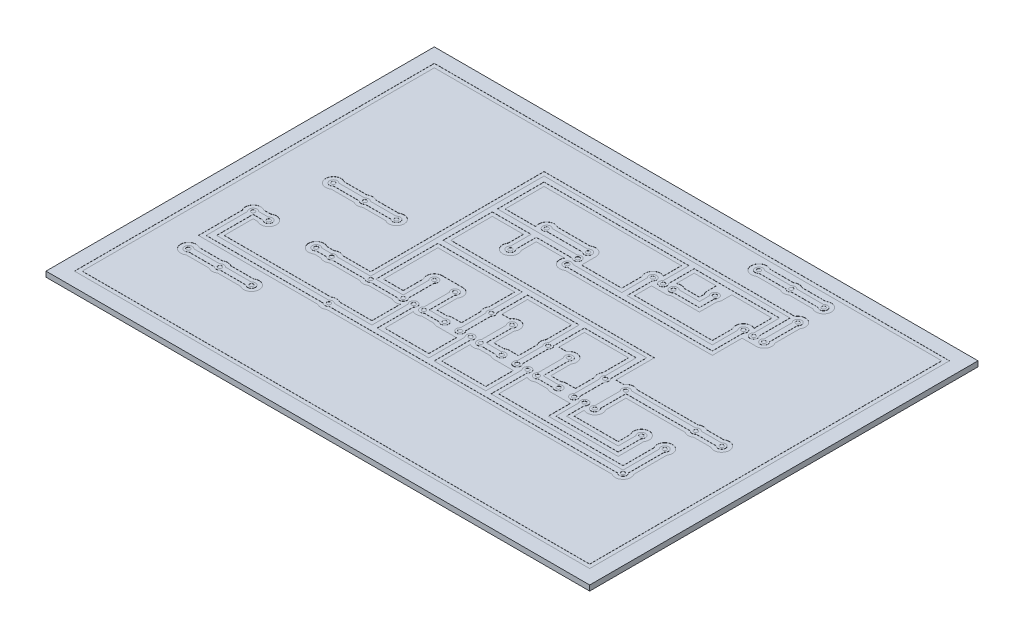
SolidWorks part; units mm, degrees
ref_plane "Front Plane" through (0, 0, 0) normal (0, 0, 1) x (1, 0, 0)
ref_plane "Top Plane" through (0, 0, 0) normal (0, 1, 0) x (1, 0, 0)
ref_plane "Right Plane" through (0, 0, 0) normal (1, 0, 0) x (0, 0, -1)
sketch "Sketch1" plane through (0, 0, 0) normal (0, 1, 0) x (1, 0, 0)
  line L0 (-86, -16.118) -> (-86, -32.118)
  line L1 (-105, 75) -> (105, 75)
  line L2 (-105, 75) -> (-105, -75)
  line L3 (-105, -75) -> (105, -75)
  line L4 (105, 75) -> (105, -75)
  line L5 (-105, 75) -> (105, -75) construction
  line L6 (-105, -75) -> (-24, -17.1429) construction
  line L7 (-86, -32.118) -> (-40.7361, -32.118)
  line L8 (75, -30) -> (75, -16.118)
  line L10 (73, -16.118) -> (73, -30)
  line L11 (72.882, -30.118) -> (22, -30.118)
  line L12 (22, -30.118) -> (22, -16.118)
  line L14 (20, -16.118) -> (20, -30.118)
  line L15 (20, -30.118) -> (0, -30.118)
  line L16 (0, -30.118) -> (0, -16.118)
  line L18 (-2, -16.118) -> (-2, -30.118)
  line L19 (-2, -30.118) -> (-22, -30.118)
  line L20 (-22, -30.118) -> (-22, -16.118)
  line L22 (-24, -16.118) -> (-24, -30.118)
  line L23 (-24, -30.118) -> (-38.5, -30.118)
  line L24 (-84, -30.118) -> (-84, -16.118)
  line L26 (-24, -17.1429) -> (-21.5529, -15.3949) construction
  line L27 (-21.5529, -15.3949) -> (105, 75) construction
  line L32 (-20, -13.882) -> (-20, -4.118)
  line L34 (-18, -4.118) -> (-18, -13.882)
  line L36 (-26, -4.118) -> (-26, -13.882)
  line L37 (-28, -13.882) -> (-28, -4.118)
  line L38 (-28.118, -16) -> (-38.5, -16)
  line L40 (-53.5, -14) -> (-40.7361, -14)
  line L42 (-38.5, -14) -> (-28.118, -14)
  line L43 (-40.7361, -16) -> (-53.5, -16)
  line L44 (4, -4.118) -> (4, -13.882)
  line L45 (2, -13.882) -> (2, -4.118)
  line L46 (-6, -13.882) -> (-6, -4.118)
  line L47 (-4, -4.118) -> (-4, -13.882)
  line L48 (24, -13.882) -> (24, -4.118)
  line L49 (16, -13.882) -> (16, -4.118)
  line L50 (26, -4.118) -> (26, -13.882)
  line L51 (18, -4.118) -> (18, -13.882)
  line L52 (48, -4.118) -> (48, -13.882)
  line L53 (38, -13.882) -> (38, -4.118)
  line L54 (46, -13.882) -> (46, -4.118)
  line L55 (40, -4.118) -> (40, -13.882)
  line L56 (44, -16.118) -> (44, -23)
  line L57 (44, -23) -> (64, -23)
  line L58 (64, -23) -> (64, -16.118)
  line L60 (66, -16.118) -> (66, -25)
  line L61 (66, -25) -> (42, -25)
  line L62 (42, -25) -> (42, -16.118)
  line L64 (40, -1.882) -> (40, 12)
  line L65 (40, 12) -> (-38.618, 12)
  line L67 (-38.618, -13.882) -> (-38.618, 10)
  line L68 (-40.618, 10) -> (-40.618, -13.882)
  line L69 (-38.618, 10) -> (-6, 10)
  line L70 (-6, 10) -> (-6, -1.882)
  line L72 (-4, -1.882) -> (-4, 10)
  line L73 (-4, 10) -> (16, 10)
  line L74 (16, 10) -> (16, -1.882)
  line L76 (18, -1.882) -> (18, 10)
  line L77 (18, 10) -> (38, 10)
  line L78 (38, 10) -> (38, -1.882)
  line L79 (48.118, -4) -> (72.882, -4)
  line L80 (-38.618, 12) -> (-38.618, 31)
  line L81 (72.882, -2) -> (48.118, -2)
  line L82 (-38.618, 31) -> (-23.618, 31)
  line L83 (-23.618, 31) -> (-23.618, 23.118)
  line L85 (-21.618, 23.118) -> (-21.618, 31)
  line L86 (-21.618, 31) -> (-7.7361, 31)
  line L88 (-7.7361, 33) -> (-38.618, 33)
  line L89 (-38.618, 33) -> (-38.618, 51)
  line L90 (-38.618, 51) -> (17.382, 51)
  line L91 (17.382, 51) -> (17.382, 41.118)
  line L93 (19.382, 41.118) -> (19.382, 51)
  line L94 (19.382, 51) -> (52.382, 51)
  line L95 (52.382, 51) -> (52.382, 41.118)
  line L97 (54.382, 41.118) -> (54.382, 53)
  line L98 (54.382, 53) -> (-40.618, 53)
  line L99 (-40.618, 53) -> (-40.618, 10)
  line L101 (-5.5, 29) -> (13.382, 29)
  line L102 (13.382, 29) -> (13.382, 38.882)
  line L104 (15.382, 38.882) -> (15.382, 29)
  line L105 (15.382, 29) -> (48.382, 29)
  line L106 (48.382, 29) -> (48.382, 38.882)
  line L108 (50.382, 38.882) -> (50.382, 27)
  line L109 (50.382, 27) -> (-5.5, 27)
  line L116 (56.2639, 62) -> (46, 62)
  line L118 (33.5, 64) -> (43.7639, 64)
  line L119 (23.5, 39) -> (31.382, 39)
  line L121 (31.382, 41) -> (23.5, 41)
  line L124 (-7.7361, 37) -> (-21.5, 37)
  line L126 (-21.5, 35) -> (-7.7361, 35)
  line L127 (58.382, 41.118) -> (58.382, 51.882)
  line L128 (56.382, 41.118) -> (56.382, 51.882)
  line L129 (-17.882, -14) -> (-12.118, -14)
  line L131 (-12.118, -16) -> (-17.882, -16)
  line L132 (4.118, -14) -> (9.882, -14)
  line L134 (9.882, -16) -> (4.118, -16)
  line L136 (26.118, -14) -> (31.882, -14)
  line L138 (31.882, -16) -> (26.118, -16)
  line L139 (-40.7361, -30.118) -> (-84, -30.118)
  line L140 (-38.5, -32.118) -> (72.882, -32.118)
  line L141 (-55.7361, -14) -> (-59.5, -14)
  line L143 (-59.5, -16) -> (-55.7361, -16)
  line L145 (-55.7361, 9) -> (-65.691, 9)
  line L147 (-77.882, 11) -> (-67.9271, 11)
  line L149 (-61.7361, -41) -> (-71.691, -41)
  line L150 (-83.882, -39) -> (-73.9271, -39)
  line L151 (-83.882, -16) -> (-80.118, -16)
  line L153 (-80.118, -14) -> (-83.882, -14)
  line L154 (-71.691, -39) -> (-61.7361, -39)
  line L155 (-73.9271, -41) -> (-83.882, -41)
  line L156 (-60.618, -40) -> (-85, -40) construction
  line L157 (-67.9271, 9) -> (-77.882, 9)
  line L158 (-65.691, 11) -> (-55.7361, 11)
  line L159 (-79, 10) -> (-54.618, 10) construction
  line L160 (75.118, -2) -> (82.882, -2)
  line L162 (82.882, -4) -> (75.118, -4)
  line L163 (46, 64) -> (56.2639, 64)
  line L164 (43.7639, 62) -> (33.5, 62)
  line L165 (57.382, 63) -> (32.382, 63) construction
  line L167 (31.382, 39) -> (33.382, 39)
  line L168 (33.382, 39) -> (33.382, 44.882)
  line L170 (31.382, 44.882) -> (31.382, 41)
  arc A1 (-84, -16.118) -> (-83.882, -16) centre (-85, -15) ccw
  circle A2 centre (-85, -15) radius 0.75
  circle A3 centre (-23, -15) radius 0.75
  arc A4 (-22, -16.118) -> (-22, -13.882) centre (-23, -15) ccw
  circle A5 centre (-1, -15) radius 0.75
  arc A6 (0, -16.118) -> (-2, -16.118) centre (-1, -15) ccw
  circle A7 centre (21, -15) radius 0.75
  arc A8 (22, -16.118) -> (20, -16.118) centre (21, -15) ccw
  circle A9 centre (74, -15) radius 0.75
  arc A10 (75, -16.118) -> (73, -16.118) centre (74, -15) ccw
  arc A11 (-24, -13.882) -> (-24, -16.118) centre (-23, -15) ccw
  circle A14 centre (-19, -15) radius 0.75
  arc A15 (-20, -13.882) -> (-17.882, -16) centre (-19, -15) ccw
  circle A16 centre (-19, -3) radius 0.75
  arc A17 (-18, -4.118) -> (-20, -4.118) centre (-19, -3) ccw
  circle A18 centre (-27, -3) radius 0.75
  circle A19 centre (-27, -15) radius 0.75
  arc A20 (-28, -13.882) -> (-28.118, -14) centre (-27, -15) ccw
  arc A21 (-26, -4.118) -> (-28, -4.118) centre (-27, -3) ccw
  circle A23 centre (-39.618, -15) radius 0.75
  arc A24 (-38.5, -14) -> (-38.618, -13.882) centre (-39.618, -15) ccw
  arc A25 (-40.7361, -16) -> (-38.5, -16) centre (-39.618, -15) ccw
  arc A26 (-28.118, -16) -> (-26, -13.882) centre (-27, -15) ccw
  circle A27 centre (3, -3) radius 0.75
  circle A28 centre (3, -15) radius 0.75
  arc A29 (2, -13.882) -> (4.118, -16) centre (3, -15) ccw
  arc A30 (4, -4.118) -> (2, -4.118) centre (3, -3) ccw
  circle A31 centre (-5, -15) radius 0.75
  arc A32 (-6, -13.882) -> (-4, -13.882) centre (-5, -15) ccw
  arc A33 (-4, -4.118) -> (-4, -1.882) centre (-5, -3) ccw
  circle A34 centre (-5, -3) radius 0.75
  arc A35 (16, -13.882) -> (18, -13.882) centre (17, -15) ccw
  circle A36 centre (17, -15) radius 0.75
  circle A37 centre (17, -3) radius 0.75
  arc A38 (24, -13.882) -> (26.118, -16) centre (25, -15) ccw
  circle A39 centre (25, -3) radius 0.75
  circle A40 centre (25, -15) radius 0.75
  arc A41 (18, -4.118) -> (18, -1.882) centre (17, -3) ccw
  arc A42 (26, -4.118) -> (24, -4.118) centre (25, -3) ccw
  circle A43 centre (39, -3) radius 0.75
  arc A44 (48, -4.118) -> (48.118, -4) centre (47, -3) ccw
  arc A45 (40, -4.118) -> (40, -1.882) centre (39, -3) ccw
  circle A46 centre (47, -3) radius 0.75
  circle A47 centre (47, -15) radius 0.75
  circle A48 centre (39, -15) radius 0.75
  arc A49 (46, -13.882) -> (48, -13.882) centre (47, -15) ccw
  arc A50 (38, -13.882) -> (40, -13.882) centre (39, -15) ccw
  circle A51 centre (43, -15) radius 0.75
  arc A52 (44, -16.118) -> (42, -16.118) centre (43, -15) ccw
  circle A53 centre (65, -15) radius 0.75
  arc A54 (66, -16.118) -> (64, -16.118) centre (65, -15) ccw
  arc A55 (-40.618, -13.882) -> (-40.7361, -14) centre (-39.618, -15) ccw
  arc A56 (38, -1.882) -> (38, -4.118) centre (39, -3) ccw
  arc A57 (16, -1.882) -> (16, -4.118) centre (17, -3) ccw
  arc A58 (-6, -1.882) -> (-6, -4.118) centre (-5, -3) ccw
  circle A59 centre (-54.618, -15) radius 0.75
  arc A60 (-53.5, -14) -> (-55.7361, -14) centre (-54.618, -15) ccw
  circle A61 centre (74, -3) radius 0.75
  arc A62 (72.882, -4) -> (75.118, -4) centre (74, -3) ccw
  arc A63 (48.118, -2) -> (46, -4.118) centre (47, -3) ccw
  circle A64 centre (-6.618, 36) radius 0.75
  arc A65 (-7.7361, 35) -> (-7.7361, 37) centre (-6.618, 36) ccw
  circle A66 centre (-22.618, 36) radius 0.75
  arc A67 (-21.5, 37) -> (-21.5, 35) centre (-22.618, 36) ccw
  circle A68 centre (-6.618, 32) radius 0.75
  arc A69 (-7.7361, 31) -> (-7.7361, 33) centre (-6.618, 32) ccw
  circle A70 centre (-22.618, 22) radius 0.75
  arc A71 (-23.618, 23.118) -> (-21.618, 23.118) centre (-22.618, 22) ccw
  circle A72 centre (-6.618, 28) radius 0.75
  arc A73 (-5.5, 29) -> (-5.5, 27) centre (-6.618, 28) ccw
  circle A74 centre (14.382, 40) radius 0.75
  arc A75 (15.382, 38.882) -> (13.382, 38.882) centre (14.382, 40) ccw
  circle A76 centre (18.382, 40) radius 0.75
  arc A77 (17.382, 41.118) -> (19.382, 41.118) centre (18.382, 40) ccw
  circle A78 centre (22.382, 40) radius 0.75
  arc A79 (23.5, 41) -> (23.5, 39) centre (22.382, 40) ccw
  circle A82 centre (49.382, 40) radius 0.75
  arc A83 (50.382, 38.882) -> (48.382, 38.882) centre (49.382, 40) ccw
  circle A84 centre (53.382, 40) radius 0.75
  arc A85 (52.382, 41.118) -> (54.382, 41.118) centre (53.382, 40) ccw
  circle A86 centre (57.382, 40) radius 0.75
  arc A87 (56.382, 41.118) -> (58.382, 41.118) centre (57.382, 40) ccw
  circle A88 centre (57.382, 53) radius 0.75
  arc A89 (58.382, 51.882) -> (56.382, 51.882) centre (57.382, 53) ccw
  circle A90 centre (57.382, 63) radius 0.75
  arc A91 (56.2639, 62) -> (56.2639, 64) centre (57.382, 63) ccw
  circle A92 centre (32.382, 63) radius 0.75
  arc A93 (33.5, 64) -> (33.5, 62) centre (32.382, 63) ccw
  arc A94 (-17.882, -14) -> (-18, -13.882) centre (-19, -15) ccw
  arc A95 (-12.118, -16) -> (-12.118, -14) centre (-11, -15) ccw
  circle A96 centre (-11, -15) radius 0.75
  circle A97 centre (11, -15) radius 0.75
  arc A98 (9.882, -16) -> (9.882, -14) centre (11, -15) ccw
  arc A99 (4.118, -14) -> (4, -13.882) centre (3, -15) ccw
  circle A100 centre (33, -15) radius 0.75
  arc A101 (31.882, -16) -> (31.882, -14) centre (33, -15) ccw
  arc A102 (26.118, -14) -> (26, -13.882) centre (25, -15) ccw
  circle A103 centre (-39.618, -31.118) radius 0.75
  arc A104 (-38.5, -30.118) -> (-40.7361, -30.118) centre (-39.618, -31.118) ccw
  circle A105 centre (74, -31.118) radius 0.75
  arc A106 (73, -30) -> (72.882, -30.118) centre (74, -31.118) ccw
  circle A109 centre (-54.618, 10) radius 0.75
  arc A110 (-55.7361, 9) -> (-55.7361, 11) centre (-54.618, 10) ccw
  arc A111 (-40.7361, -32.118) -> (-38.5, -32.118) centre (-39.618, -31.118) ccw
  arc A112 (72.882, -32.118) -> (75, -30) centre (74, -31.118) ccw
  circle A113 centre (-60.618, -15) radius 0.75
  arc A114 (-59.5, -14) -> (-59.5, -16) centre (-60.618, -15) ccw
  arc A115 (-55.7361, -16) -> (-53.5, -16) centre (-54.618, -15) ccw
  circle A116 centre (-79, 10) radius 0.75
  arc A117 (-77.882, 11) -> (-77.882, 9) centre (-79, 10) ccw
  circle A118 centre (-60.618, -40) radius 0.75
  arc A119 (-61.7361, -41) -> (-61.7361, -39) centre (-60.618, -40) ccw
  circle A120 centre (-85, -40) radius 0.75
  arc A121 (-83.882, -39) -> (-83.882, -41) centre (-85, -40) ccw
  circle A122 centre (-79, -15) radius 0.75
  arc A123 (-80.118, -16) -> (-80.118, -14) centre (-79, -15) ccw
  arc A124 (-83.882, -14) -> (-86, -16.118) centre (-85, -15) ccw
  circle A125 centre (-66.809, 10) radius 0.75
  arc A126 (-65.691, 11) -> (-67.9271, 11) centre (-66.809, 10) ccw
  arc A127 (-71.691, -39) -> (-73.9271, -39) centre (-72.809, -40) ccw
  circle A128 centre (-72.809, -40) radius 0.75
  arc A129 (-73.9271, -41) -> (-71.691, -41) centre (-72.809, -40) ccw
  arc A130 (-67.9271, 9) -> (-65.691, 9) centre (-66.809, 10) ccw
  arc A131 (-22, -13.882) -> (-24, -13.882) centre (-23, -15) ccw
  circle A132 centre (84, -3) radius 0.75
  arc A133 (82.882, -4) -> (82.882, -2) centre (84, -3) ccw
  arc A134 (75.118, -2) -> (72.882, -2) centre (74, -3) ccw
  arc A135 (46, 64) -> (43.7639, 64) centre (44.882, 63) ccw
  circle A136 centre (44.882, 63) radius 0.75
  arc A137 (43.7639, 62) -> (46, 62) centre (44.882, 63) ccw
  circle A138 centre (32.382, 46) radius 0.75
  arc A139 (33.382, 44.882) -> (31.382, 44.882) centre (32.382, 46) ccw
  point P0 (0, 0)
  point P289 (-66.809, 10)
  point P290 (-72.809, -40)
  point P291 (44.882, 63)
  dimension "D1" = 150
  dimension "D3" = 3
  dimension "D6" = 1.5
  dimension "D15" = 3
  dimension "D16" = 1.5
  dimension "D17" = 3
  dimension "D18" = 1.5
  dimension "D19" = 3
  dimension "D20" = 1.5
  dimension "D21" = 1.5
  dimension "D22" = 3
  dimension "D26" = 15
  dimension "D27" = 10
  dimension "D29" = 1.5
  dimension "D30" = 3
  dimension "D33" = 3
  dimension "D34" = 1.5
  dimension "D35" = 1.5
  dimension "D36" = 1.5
  dimension "D43" = 1.5
  dimension "D44" = 3
  dimension "D52" = 4
  dimension "D59" = 3
  dimension "D60" = 1.5
  dimension "D61" = 3
  dimension "D62" = 1.5
  dimension "D71" = 15
  dimension "D89" = 4
  dimension "D90" = 3
  dimension "D84" = 4
  dimension "D116" = 3
  dimension "D117" = 1.5
  dimension "D100" = 1.5
  dimension "D2" = 210
  dimension "D4" = 15
  dimension "D5" = 20
  dimension "D7" = 2
  dimension "D8" = 2
  dimension "D9" = 2
  dimension "D10" = 60
  dimension "D11" = 20
  dimension "D12" = 20
  dimension "D13" = 8
  dimension "D14" = 14
  dimension "D23" = 2
  dimension "D24" = 2
  dimension "D25" = 25
  dimension "D28" = 4
  dimension "D31" = 2
  dimension "D32" = 12
  dimension "D37" = 26
  dimension "D38" = 27
  dimension "D39" = 3
  dimension "D40" = 13.882
  dimension "D41" = 2
  dimension "D42" = 2
  dimension "D45" = 38.5
  dimension "D46" = 2
  dimension "D47" = 2
  dimension "D48" = 2
  dimension "D49" = 4
  dimension "D50" = 4
  dimension "D51" = 4
  dimension "D53" = 2
  dimension "D54" = 2
  dimension "D55" = 2
  dimension "D56" = 2
  dimension "D57" = 2
  dimension "D58" = 2
  dimension "D63" = 20
  dimension "D64" = 4
  dimension "D65" = 4
  dimension "D66" = 20
  dimension "D67" = 8
  dimension "D68" = 10
  dimension "D69" = 2
  dimension "D70" = 2
  dimension "D72" = 2
  dimension "D73" = 2
  dimension "D74" = 2
  dimension "D75" = 2
  dimension "D76" = 2
  dimension "D77" = 2
  dimension "D78" = 2
  dimension "D79" = 2
  dimension "D80" = 2
  dimension "D81" = 2
  dimension "D82" = 2
  dimension "D83" = 2
  dimension "D85" = 2
  dimension "D86" = 4
  dimension "D87" = 2
  dimension "D88" = 4
  dimension "D91" = 2
  dimension "D92" = 10
  dimension "D93" = 4
  dimension "D94" = 4
  dimension "D95" = 10
  dimension "D96" = 15
  dimension "D97" = 20
  dimension "D98" = 10
  dimension "D99" = 15
  dimension "D101" = 10
  dimension "D102" = 8
  dimension "D103" = 8
  dimension "D104" = 8
  dimension "D105" = 1
  dimension "D106" = 25
  dimension "D107" = 2
  dimension "D108" = 2
  dimension "D109" = 25
  dimension "D110" = 6
  dimension "D111" = 5
  dimension "D112" = 15
  dimension "D114" = 2
  dimension "D115" = 6
extrude "Boss-Extrude3" add sketch "Sketch1" along normal blind 2 contours L1 L4 L3 L2
extrude "Boss-Extrude4" add sketch "Sketch1<5>" along normal blind 2.05 contours A11 L22 L23 L24 A1 L0 L7 L8 A10 L10 L11 L12 A8 L14 L15 L16 A6 L18 L19 L20 A4 A2 A3 A5 A7 A9 | L60 A54 L58 L57 L56 A52 L62 L61 A51 A53 | L54 A49 L52 A44 A46 A47 | L53 A50 L55 A45 A43 A48 | L50 A42 L48 A38 A39 A40 | L51 A41 L49 A35 A36 A37 | L44 A30 L45 A29 A27 A28 | L47 A33 L46 A32 A34 A31 | L34 A17 L32 A15 A14 A16 | L38 A26 L36 A21 L37 A20 L42 A24 L40 L43 A25 A18 A19 A23 | L118 A93 L116 A91 A90 A92 | L124 A67 L126 A65 A64 A66 | L108 A83 L106 L105 L104 A75 L102 L101 A73 L109 A72 A74 A82 | L119 L121 A79 A78 A138 | L127 A89 L128 A87 A86 A88 | L157 A130 L145 A110 L158 A126 L147 A117 A109 A116 A125 | L155 A129 L149 A119 L154 A127 L150 A121 A118 A120 A128 region at (-85.9453, 0, 14.0547) region at (-19.814, 0, 9) region at (-27.3609, 0, 9) region at (3.814, 0, 9) region at (24.186, 0, 9) region at (47.5728, 0, 9) region at (43.7248, 0, 19.559) region at (3.941, 0, -28.3912) region at (51.132, 0, -62.2816) region at (21.0401, 0, -40) region at (-14.618, 0, -36) region at (57.382, 0, -46.5) region at (-60.7135, 0, -9.2755) region at (-66.7135, 0, 40.7245)
sketch "Sketch1<5>" plane through (0, 0, 0) normal (0, 1, 0) x (1, 0, 0) same geometry as "Sketch1"
sketch "Sketch2" plane through (0, 2, 0) normal (0, 1, 0) x (1, 0, 0)
  line L0 (41.5, -1.3417) -> (44.5, -1.3417)
  line L1 (-105, 75) -> (105, 75)
  line L2 (-105, 75) -> (-105, -75)
  line L3 (-105, -75) -> (105, -75)
  line L4 (59.882, 41.6583) -> (59.882, 51.3417)
  line L5 (54.882, 51.3417) -> (54.882, 41.6583)
  line L6 (59.882, 41.6583) -> (59.882, 51.3417)
  line L8 (105, 75) -> (105, -75)
  line L9 (19.5, -1.3417) -> (22.5, -1.3417)
  line L10 (-2.5, -1.3417) -> (0.5, -1.3417)
  line L11 (-27, 0) -> (-19, 0)
  line L12 (57.382, 37) -> (51.882, 37)
  line L13 (22.382, 37) -> (16.882, 37)
  line L14 (34.0403, 60.5) -> (43.2237, 60.5)
  line L15 (46.5403, 60.5) -> (55.7237, 60.5)
  line L16 (55.7237, 65.5) -> (46.5403, 65.5)
  line L17 (43.2237, 65.5) -> (34.0403, 65.5)
  line L18 (34.0403, 60.5) -> (43.2237, 60.5)
  line L19 (46.5403, 60.5) -> (55.7237, 60.5)
  line L20 (55.7237, 65.5) -> (46.5403, 65.5)
  line L21 (43.2237, 65.5) -> (34.0403, 65.5)
  line L22 (-3.618, 36) -> (-3.618, 30.5)
  line L23 (29.382, 46) -> (29.382, 49.5)
  line L24 (35.382, 46) -> (35.382, 49.5)
  line L25 (-11, -18) -> (-5, -18)
  line L26 (-11, -12) -> (-7.5, -12)
  line L27 (11, -12) -> (14.5, -12)
  line L28 (33, -12) -> (36.5, -12)
  line L29 (33, -18) -> (40.5, -18)
  line L30 (11, -18) -> (18.5, -18)
  line L31 (-5, -18) -> (-3.5, -18)
  line L74 (-17.3417, -17.5) -> (-12.6583, -17.5)
  line L75 (-12.6583, -12.5) -> (-16.5, -12.5)
  line L76 (-16.5, -12.5) -> (-16.5, -4.6583)
  line L77 (-21.5, -4.6583) -> (-21.5, -13.3417)
  line L78 (-17.3417, -17.5) -> (-12.6583, -17.5)
  line L79 (-12.6583, -12.5) -> (-16.5, -12.5)
  line L80 (-16.5, -12.5) -> (-16.5, -4.6583)
  line L85 (-25.5, -16.6583) -> (-25.5, -28.618)
  line L86 (-25.5, -28.618) -> (-37.9597, -28.618)
  line L87 (-58.9597, -17.5) -> (-56.2763, -17.5)
  line L88 (-52.9597, -17.5) -> (-41.2763, -17.5)
  line L89 (-37.9597, -17.5) -> (-28.6583, -17.5)
  line L90 (-24.5, -13.3417) -> (-24.5, -4.6583)
  line L91 (-29.5, -4.6583) -> (-29.5, -12.5)
  line L92 (-29.5, -12.5) -> (-37.118, -12.5)
  line L93 (-37.118, -12.5) -> (-37.118, 8.5)
  line L94 (-37.118, 8.5) -> (-7.5, 8.5)
  line L95 (-7.5, 8.5) -> (-7.5, -1.3417)
  line L96 (-7.5, -4.6583) -> (-7.5, -13.3417)
  line L97 (-2.5, -13.3417) -> (-2.5, -4.6583)
  line L98 (-2.5, -1.3417) -> (-2.5, 8.5)
  line L99 (-2.5, 8.5) -> (14.5, 8.5)
  line L100 (14.5, 8.5) -> (14.5, -1.3417)
  line L101 (14.5, -4.6583) -> (14.5, -13.3417)
  line L102 (19.5, -13.3417) -> (19.5, -4.6583)
  line L103 (19.5, -1.3417) -> (19.5, 8.5)
  line L104 (19.5, 8.5) -> (36.5, 8.5)
  line L105 (36.5, 8.5) -> (36.5, -1.3417)
  line L106 (36.5, -4.6583) -> (36.5, -13.3417)
  line L107 (41.5, -13.3417) -> (41.5, -4.6583)
  line L108 (41.5, -1.3417) -> (41.5, 13.5)
  line L109 (41.5, 13.5) -> (-37.118, 13.5)
  line L110 (-37.118, 13.5) -> (-37.118, 29.5)
  line L111 (-37.118, 29.5) -> (-25.118, 29.5)
  line L112 (-25.118, 29.5) -> (-25.118, 23.6583)
  line L113 (-20.118, 23.6583) -> (-20.118, 29.5)
  line L114 (-20.118, 29.5) -> (-8.2763, 29.5)
  line L115 (-8.2763, 34.5) -> (-37.118, 34.5)
  line L116 (-37.118, 34.5) -> (-37.118, 49.5)
  line L117 (-37.118, 49.5) -> (15.882, 49.5)
  line L118 (15.882, 49.5) -> (15.882, 41.6583)
  line L119 (20.882, 41.6583) -> (20.882, 49.5)
  line L120 (20.882, 49.5) -> (50.882, 49.5)
  line L121 (50.882, 49.5) -> (50.882, 41.6583)
  line L122 (55.882, 41.6583) -> (55.882, 54.5)
  line L123 (55.882, 54.5) -> (-42.118, 54.5)
  line L124 (-42.118, 54.5) -> (-42.118, -12.5)
  line L125 (-42.118, -12.5) -> (-52.9597, -12.5)
  line L126 (-56.2763, -12.5) -> (-58.9597, -12.5)
  line L127 (-58.9597, -17.5) -> (-56.2763, -17.5)
  line L128 (-52.9597, -17.5) -> (-41.2763, -17.5)
  line L129 (-37.9597, -17.5) -> (-28.6583, -17.5)
  line L131 (-29.5, -4.6583) -> (-29.5, -12.5)
  line L132 (-29.5, -12.5) -> (-37.118, -12.5)
  line L133 (-37.118, -12.5) -> (-37.118, 8.5)
  line L134 (-37.118, 8.5) -> (-7.5, 8.5)
  line L135 (-7.5, 8.5) -> (-7.5, -1.3417)
  line L136 (-7.5, -4.6583) -> (-7.5, -12)
  line L138 (-2.5, -1.3417) -> (-2.5, 8.5)
  line L139 (-2.5, 8.5) -> (14.5, 8.5)
  line L140 (14.5, 8.5) -> (14.5, -1.3417)
  line L141 (14.5, -4.6583) -> (14.5, -12)
  line L143 (19.5, -1.3417) -> (19.5, 8.5)
  line L144 (19.5, 8.5) -> (36.5, 8.5)
  line L145 (36.5, 8.5) -> (36.5, -1.3417)
  line L146 (36.5, -4.6583) -> (36.5, -12)
  line L148 (41.5, -1.3417) -> (41.5, 13.5)
  line L149 (41.5, 13.5) -> (-37.118, 13.5)
  line L150 (-37.118, 13.5) -> (-37.118, 29.5)
  line L151 (-37.118, 29.5) -> (-25.118, 29.5)
  line L152 (-25.118, 29.5) -> (-25.118, 23.6583)
  line L153 (-20.118, 23.6583) -> (-20.118, 29.5)
  line L154 (-20.118, 29.5) -> (-9.2161, 29.5)
  line L155 (-25.2161, 34.5) -> (-37.118, 34.5)
  line L156 (-37.118, 34.5) -> (-37.118, 49.5)
  line L157 (-37.118, 49.5) -> (15.882, 49.5)
  line L158 (15.882, 49.5) -> (15.882, 42.5981)
  line L159 (20.882, 42.5981) -> (20.882, 49.5)
  line L160 (20.882, 49.5) -> (50.882, 49.5)
  line L161 (50.882, 49.5) -> (50.882, 42.5981)
  line L163 (54.7839, 54.5) -> (-42.118, 54.5)
  line L164 (-42.118, 54.5) -> (-42.118, -12.5)
  line L165 (-42.118, -12.5) -> (-52.9597, -12.5)
  line L166 (-56.2763, -12.5) -> (-58.9597, -12.5)
  line L167 (-41.2763, -28.618) -> (-82.5, -28.618)
  line L168 (-82.5, -28.618) -> (-82.5, -17.5)
  line L169 (-82.5, -17.5) -> (-80.6583, -17.5)
  line L170 (-80.6583, -12.5) -> (-83.3417, -12.5)
  line L171 (-87.5, -16.6583) -> (-87.5, -33.618)
  line L172 (-87.5, -33.618) -> (-41.2763, -33.618)
  line L173 (-37.9597, -33.618) -> (72.3417, -33.618)
  line L174 (76.5, -29.4597) -> (76.5, -16.6583)
  line L175 (71.5, -16.6583) -> (71.5, -28.618)
  line L176 (71.5, -28.618) -> (23.5, -28.618)
  line L177 (23.5, -28.618) -> (23.5, -16.6583)
  line L178 (18.5, -16.6583) -> (18.5, -28.618)
  line L179 (18.5, -28.618) -> (1.5, -28.618)
  line L180 (1.5, -28.618) -> (1.5, -16.6583)
  line L181 (-3.5, -16.6583) -> (-3.5, -28.618)
  line L182 (-3.5, -28.618) -> (-20.5, -28.618)
  line L183 (-20.5, -28.618) -> (-20.5, -16.6583)
  line L184 (-25.5, -17.5981) -> (-25.5, -28.618)
  line L185 (-25.5, -28.618) -> (-37.9597, -28.618)
  line L186 (-41.2763, -28.618) -> (-82.5, -28.618)
  line L187 (-82.5, -28.618) -> (-82.5, -17.5)
  line L188 (-82.5, -17.5) -> (-80.6583, -17.5)
  line L189 (-80.6583, -12.5) -> (-83.3417, -12.5)
  line L190 (-87.5, -16.6583) -> (-87.5, -33.618)
  line L191 (-87.5, -33.618) -> (-41.2763, -33.618)
  line L192 (-37.9597, -33.618) -> (72.3417, -33.618)
  line L193 (76.5, -29.4597) -> (76.5, -16.6583)
  line L194 (71.5, -16.6583) -> (71.5, -28.618)
  line L195 (71.5, -28.618) -> (23.5, -28.618)
  line L196 (23.5, -28.618) -> (23.5, -16.6583)
  line L197 (18.5, -18) -> (18.5, -28.618)
  line L198 (18.5, -28.618) -> (1.5, -28.618)
  line L199 (1.5, -28.618) -> (1.5, -17.5981)
  line L200 (-3.5, -18) -> (-3.5, -28.618)
  line L201 (-3.5, -28.618) -> (-20.5, -28.618)
  line L202 (-20.5, -28.618) -> (-20.5, -17.5981)
  line L204 (9.3417, -12.5) -> (5.5, -12.5)
  line L205 (5.5, -12.5) -> (5.5, -4.6583)
  line L206 (0.5, -4.6583) -> (0.5, -13.3417)
  line L207 (4.6583, -17.5) -> (9.3417, -17.5)
  line L208 (9.3417, -12.5) -> (5.5, -12.5)
  line L209 (5.5, -12.5) -> (5.5, -4.6583)
  line L211 (4.6583, -17.5) -> (9.3417, -17.5)
  line L216 (31.3417, -12.5) -> (27.5, -12.5)
  line L217 (27.5, -12.5) -> (27.5, -4.6583)
  line L218 (22.5, -4.6583) -> (22.5, -13.3417)
  line L219 (26.6583, -17.5) -> (31.3417, -17.5)
  line L220 (31.3417, -12.5) -> (27.5, -12.5)
  line L221 (27.5, -12.5) -> (27.5, -4.6583)
  line L223 (26.6583, -17.5) -> (31.3417, -17.5)
  line L232 (67.5, -26.5) -> (67.5, -16.6583)
  line L233 (62.5, -16.6583) -> (62.5, -21.5)
  line L234 (62.5, -21.5) -> (45.5, -21.5)
  line L235 (45.5, -21.5) -> (45.5, -16.6583)
  line L236 (40.5, -16.6583) -> (40.5, -26.5)
  line L237 (40.5, -26.5) -> (67.5, -26.5)
  line L238 (67.5, -26.5) -> (67.5, -16.6583)
  line L239 (62.5, -16.6583) -> (62.5, -21.5)
  line L240 (62.5, -21.5) -> (45.5, -21.5)
  line L241 (45.5, -21.5) -> (45.5, -17.5981)
  line L242 (40.5, -18) -> (40.5, -26.5)
  line L243 (40.5, -26.5) -> (67.5, -26.5)
  line L250 (82.3417, -0.5) -> (75.6583, -0.5)
  line L251 (72.3417, -0.5) -> (48.6583, -0.5)
  line L252 (44.5, -4.6583) -> (44.5, -13.3417)
  line L253 (49.5, -13.3417) -> (49.5, -5.5)
  line L254 (49.5, -5.5) -> (72.3417, -5.5)
  line L255 (75.6583, -5.5) -> (82.3417, -5.5)
  line L256 (82.3417, -0.5) -> (75.6583, -0.5)
  line L257 (72.3417, -0.5) -> (48.6583, -0.5)
  line L259 (49.5, -13.3417) -> (49.5, -5.5)
  line L260 (49.5, -5.5) -> (72.3417, -5.5)
  line L261 (75.6583, -5.5) -> (82.3417, -5.5)
  line L270 (51.882, 25.5) -> (51.882, 38.3417)
  line L271 (46.882, 38.3417) -> (46.882, 30.5)
  line L272 (46.882, 30.5) -> (16.882, 30.5)
  line L273 (16.882, 30.5) -> (16.882, 38.3417)
  line L274 (11.882, 38.3417) -> (11.882, 30.5)
  line L275 (11.882, 30.5) -> (-4.9597, 30.5)
  line L276 (-4.9597, 25.5) -> (51.882, 25.5)
  line L277 (51.882, 25.5) -> (51.882, 37)
  line L278 (46.882, 38.3417) -> (46.882, 30.5)
  line L279 (46.882, 30.5) -> (16.882, 30.5)
  line L280 (16.882, 30.5) -> (16.882, 37)
  line L281 (11.882, 38.3417) -> (11.882, 30.5)
  line L282 (11.882, 30.5) -> (-3.618, 30.5)
  line L283 (-4.9597, 25.5) -> (51.882, 25.5)
  line L285 (34.882, 37.5) -> (34.882, 44.3417)
  line L286 (29.882, 44.3417) -> (29.882, 42.5)
  line L287 (29.882, 42.5) -> (24.0403, 42.5)
  line L288 (24.0403, 37.5) -> (34.882, 37.5)
  line L289 (34.882, 37.5) -> (34.882, 44.3417)
  line L290 (29.882, 44.3417) -> (29.882, 42.5)
  line L291 (29.882, 42.5) -> (24.0403, 42.5)
  line L292 (24.0403, 37.5) -> (34.882, 37.5)
  line L293 (-8.2763, 38.5) -> (-20.9597, 38.5)
  line L294 (-20.9597, 33.5) -> (-8.2763, 33.5)
  line L295 (-8.2763, 38.5) -> (-20.9597, 38.5)
  line L303 (-77.3417, 7.5) -> (-68.4673, 7.5)
  line L304 (-65.1507, 7.5) -> (-56.2763, 7.5)
  line L305 (-56.2763, 12.5) -> (-65.1507, 12.5)
  line L306 (-68.4673, 12.5) -> (-77.3417, 12.5)
  line L307 (-77.3417, 7.5) -> (-68.4673, 7.5)
  line L308 (-65.1507, 7.5) -> (-56.2763, 7.5)
  line L309 (-56.2763, 12.5) -> (-65.1507, 12.5)
  line L310 (-68.4673, 12.5) -> (-77.3417, 12.5)
  line L315 (-83.3417, -42.5) -> (-74.4673, -42.5)
  line L316 (-71.1507, -42.5) -> (-62.2763, -42.5)
  line L317 (-62.2763, -37.5) -> (-71.1507, -37.5)
  line L318 (-74.4673, -37.5) -> (-83.3417, -37.5)
  line L319 (-83.3417, -42.5) -> (-74.4673, -42.5)
  line L320 (-71.1507, -42.5) -> (-62.2763, -42.5)
  line L321 (-62.2763, -37.5) -> (-71.1507, -37.5)
  line L322 (-74.4673, -37.5) -> (-83.3417, -37.5)
  arc A0 (22.382, 37) -> (24.0403, 37.5) centre (22.382, 40) ccw
  arc A1 (29.382, 46) -> (29.882, 44.3417) centre (32.382, 46) ccw
  arc A2 (-11, -12) -> (-12.6583, -12.5) centre (-11, -15) ccw
  arc A3 (11, -12) -> (9.3417, -12.5) centre (11, -15) ccw
  arc A4 (33, -12) -> (31.3417, -12.5) centre (33, -15) ccw
  arc A5 (59.882, 51.3417) -> (54.882, 51.3417) centre (57.382, 53) ccw
  arc A6 (54.882, 41.6583) -> (59.882, 41.6583) centre (57.382, 40) ccw
  arc A7 (59.882, 51.3417) -> (54.7839, 54.5) centre (57.382, 53) ccw
  arc A8 (57.382, 37) -> (59.882, 41.6583) centre (57.382, 40) ccw
  arc A15 (43.2237, 60.5) -> (46.5403, 60.5) centre (44.882, 63) ccw
  arc A16 (55.7237, 60.5) -> (55.7237, 65.5) centre (57.382, 63) ccw
  arc A17 (46.5403, 65.5) -> (43.2237, 65.5) centre (44.882, 63) ccw
  arc A18 (34.0403, 65.5) -> (34.0403, 60.5) centre (32.382, 63) ccw
  arc A19 (43.2237, 60.5) -> (46.5403, 60.5) centre (44.882, 63) ccw
  arc A20 (55.7237, 60.5) -> (55.7237, 65.5) centre (57.382, 63) ccw
  arc A21 (46.5403, 65.5) -> (43.2237, 65.5) centre (44.882, 63) ccw
  arc A22 (34.0403, 65.5) -> (34.0403, 60.5) centre (32.382, 63) ccw
  arc A44 (-12.6583, -17.5) -> (-12.6583, -12.5) centre (-11, -15) ccw
  arc A45 (-16.5, -4.6583) -> (-21.5, -4.6583) centre (-19, -3) ccw
  arc A46 (-21.5, -13.3417) -> (-17.3417, -17.5) centre (-19, -15) ccw
  arc A47 (-56.2763, -17.5) -> (-52.9597, -17.5) centre (-54.618, -15) ccw
  arc A48 (-41.2763, -17.5) -> (-37.9597, -17.5) centre (-39.618, -15) ccw
  arc A49 (-28.6583, -17.5) -> (-24.5, -13.3417) centre (-27, -15) ccw
  arc A50 (-24.5, -4.6583) -> (-29.5, -4.6583) centre (-27, -3) ccw
  arc A51 (-7.5, -1.3417) -> (-7.5, -4.6583) centre (-5, -3) ccw
  arc A52 (-7.5, -13.3417) -> (-2.5, -13.3417) centre (-5, -15) ccw
  arc A53 (-2.5, -4.6583) -> (-2.5, -1.3417) centre (-5, -3) ccw
  arc A54 (14.5, -1.3417) -> (14.5, -4.6583) centre (17, -3) ccw
  arc A55 (14.5, -13.3417) -> (19.5, -13.3417) centre (17, -15) ccw
  arc A56 (19.5, -4.6583) -> (19.5, -1.3417) centre (17, -3) ccw
  arc A57 (36.5, -1.3417) -> (36.5, -4.6583) centre (39, -3) ccw
  arc A58 (36.5, -13.3417) -> (41.5, -13.3417) centre (39, -15) ccw
  arc A59 (41.5, -4.6583) -> (41.5, -1.3417) centre (39, -3) ccw
  arc A60 (-25.118, 23.6583) -> (-20.118, 23.6583) centre (-22.618, 22) ccw
  arc A61 (-8.2763, 29.5) -> (-8.2763, 34.5) centre (-6.618, 32) ccw
  arc A62 (15.882, 41.6583) -> (20.882, 41.6583) centre (18.382, 40) ccw
  arc A63 (50.882, 41.6583) -> (55.882, 41.6583) centre (53.382, 40) ccw
  arc A64 (-52.9597, -12.5) -> (-56.2763, -12.5) centre (-54.618, -15) ccw
  arc A65 (-58.9597, -12.5) -> (-58.9597, -17.5) centre (-60.618, -15) ccw
  arc A66 (-56.2763, -17.5) -> (-52.9597, -17.5) centre (-54.618, -15) ccw
  arc A67 (-41.2763, -17.5) -> (-37.9597, -17.5) centre (-39.618, -15) ccw
  arc A68 (-28.6583, -17.5) -> (-25.5, -17.5981) centre (-27, -15) ccw
  arc A69 (-27, 0) -> (-29.5, -4.6583) centre (-27, -3) ccw
  arc A70 (-7.5, -1.3417) -> (-7.5, -4.6583) centre (-5, -3) ccw
  arc A73 (14.5, -1.3417) -> (14.5, -4.6583) centre (17, -3) ccw
  arc A76 (36.5, -1.3417) -> (36.5, -4.6583) centre (39, -3) ccw
  arc A79 (-25.118, 23.6583) -> (-20.118, 23.6583) centre (-22.618, 22) ccw
  arc A83 (-52.9597, -12.5) -> (-56.2763, -12.5) centre (-54.618, -15) ccw
  arc A84 (-58.9597, -12.5) -> (-58.9597, -17.5) centre (-60.618, -15) ccw
  arc A85 (-20.5, -16.6583) -> (-25.5, -16.6583) centre (-23, -15) ccw
  arc A86 (-37.9597, -28.618) -> (-41.2763, -28.618) centre (-39.618, -31.118) ccw
  arc A87 (-80.6583, -17.5) -> (-80.6583, -12.5) centre (-79, -15) ccw
  arc A88 (-83.3417, -12.5) -> (-87.5, -16.6583) centre (-85, -15) ccw
  arc A89 (-41.2763, -33.618) -> (-37.9597, -33.618) centre (-39.618, -31.118) ccw
  arc A90 (72.3417, -33.618) -> (76.5, -29.4597) centre (74, -31.118) ccw
  arc A91 (76.5, -16.6583) -> (71.5, -16.6583) centre (74, -15) ccw
  arc A92 (23.5, -16.6583) -> (18.5, -16.6583) centre (21, -15) ccw
  arc A93 (1.5, -16.6583) -> (-3.5, -16.6583) centre (-1, -15) ccw
  arc A95 (-37.9597, -28.618) -> (-41.2763, -28.618) centre (-39.618, -31.118) ccw
  arc A96 (-80.6583, -17.5) -> (-80.6583, -12.5) centre (-79, -15) ccw
  arc A97 (-83.3417, -12.5) -> (-87.5, -16.6583) centre (-85, -15) ccw
  arc A98 (-41.2763, -33.618) -> (-37.9597, -33.618) centre (-39.618, -31.118) ccw
  arc A99 (72.3417, -33.618) -> (76.5, -29.4597) centre (74, -31.118) ccw
  arc A100 (76.5, -16.6583) -> (71.5, -16.6583) centre (74, -15) ccw
  arc A103 (-12.6583, -17.5) -> (-11, -18) centre (-11, -15) ccw
  arc A104 (-16.5, -4.6583) -> (-19, 0) centre (-19, -3) ccw
  arc A105 (-20.5, -17.5981) -> (-17.3417, -17.5) centre (-19, -15) ccw
  arc A110 (5.5, -4.6583) -> (0.5, -4.6583) centre (3, -3) ccw
  arc A111 (0.5, -13.3417) -> (4.6583, -17.5) centre (3, -15) ccw
  arc A112 (9.3417, -17.5) -> (9.3417, -12.5) centre (11, -15) ccw
  arc A113 (5.5, -4.6583) -> (0.5, -1.3417) centre (3, -3) ccw
  arc A114 (1.5, -17.5981) -> (4.6583, -17.5) centre (3, -15) ccw
  arc A115 (9.3417, -17.5) -> (11, -18) centre (11, -15) ccw
  arc A120 (27.5, -4.6583) -> (22.5, -4.6583) centre (25, -3) ccw
  arc A121 (22.5, -13.3417) -> (26.6583, -17.5) centre (25, -15) ccw
  arc A122 (31.3417, -17.5) -> (31.3417, -12.5) centre (33, -15) ccw
  arc A123 (27.5, -4.6583) -> (22.5, -1.3417) centre (25, -3) ccw
  arc A124 (23.5, -17.5981) -> (26.6583, -17.5) centre (25, -15) ccw
  arc A125 (31.3417, -17.5) -> (33, -18) centre (33, -15) ccw
  arc A126 (67.5, -16.6583) -> (62.5, -16.6583) centre (65, -15) ccw
  arc A127 (45.5, -16.6583) -> (40.5, -16.6583) centre (43, -15) ccw
  arc A128 (67.5, -16.6583) -> (62.5, -16.6583) centre (65, -15) ccw
  arc A140 (75.6583, -0.5) -> (72.3417, -0.5) centre (74, -3) ccw
  arc A141 (48.6583, -0.5) -> (44.5, -4.6583) centre (47, -3) ccw
  arc A142 (44.5, -13.3417) -> (49.5, -13.3417) centre (47, -15) ccw
  arc A143 (72.3417, -5.5) -> (75.6583, -5.5) centre (74, -3) ccw
  arc A144 (82.3417, -5.5) -> (82.3417, -0.5) centre (84, -3) ccw
  arc A145 (75.6583, -0.5) -> (72.3417, -0.5) centre (74, -3) ccw
  arc A146 (48.6583, -0.5) -> (44.5, -1.3417) centre (47, -3) ccw
  arc A147 (45.5, -17.5981) -> (49.5, -13.3417) centre (47, -15) ccw
  arc A148 (72.3417, -5.5) -> (75.6583, -5.5) centre (74, -3) ccw
  arc A149 (82.3417, -5.5) -> (82.3417, -0.5) centre (84, -3) ccw
  arc A150 (51.882, 38.3417) -> (46.882, 38.3417) centre (49.382, 40) ccw
  arc A151 (16.882, 38.3417) -> (11.882, 38.3417) centre (14.382, 40) ccw
  arc A152 (-4.9597, 30.5) -> (-4.9597, 25.5) centre (-6.618, 28) ccw
  arc A153 (50.882, 42.5981) -> (46.882, 38.3417) centre (49.382, 40) ccw
  arc A154 (15.882, 42.5981) -> (11.882, 38.3417) centre (14.382, 40) ccw
  arc A155 (-9.2161, 29.5) -> (-4.9597, 25.5) centre (-6.618, 28) ccw
  arc A157 (34.882, 44.3417) -> (29.882, 44.3417) centre (32.382, 46) ccw
  arc A158 (24.0403, 42.5) -> (24.0403, 37.5) centre (22.382, 40) ccw
  arc A159 (34.882, 44.3417) -> (35.382, 46) centre (32.382, 46) ccw
  arc A160 (24.0403, 42.5) -> (20.882, 42.5981) centre (22.382, 40) ccw
  arc A163 (-20.9597, 38.5) -> (-20.9597, 33.5) centre (-22.618, 36) ccw
  arc A164 (-8.2763, 33.5) -> (-8.2763, 38.5) centre (-6.618, 36) ccw
  arc A165 (-20.9597, 38.5) -> (-25.2161, 34.5) centre (-22.618, 36) ccw
  arc A166 (-3.618, 36) -> (-8.2763, 38.5) centre (-6.618, 36) ccw
  arc A173 (-68.4673, 7.5) -> (-65.1507, 7.5) centre (-66.809, 10) ccw
  arc A174 (-56.2763, 7.5) -> (-56.2763, 12.5) centre (-54.618, 10) ccw
  arc A175 (-65.1507, 12.5) -> (-68.4673, 12.5) centre (-66.809, 10) ccw
  arc A176 (-77.3417, 12.5) -> (-77.3417, 7.5) centre (-79, 10) ccw
  arc A177 (-68.4673, 7.5) -> (-65.1507, 7.5) centre (-66.809, 10) ccw
  arc A178 (-56.2763, 7.5) -> (-56.2763, 12.5) centre (-54.618, 10) ccw
  arc A179 (-65.1507, 12.5) -> (-68.4673, 12.5) centre (-66.809, 10) ccw
  arc A180 (-77.3417, 12.5) -> (-77.3417, 7.5) centre (-79, 10) ccw
  arc A185 (-74.4673, -42.5) -> (-71.1507, -42.5) centre (-72.809, -40) ccw
  arc A186 (-62.2763, -42.5) -> (-62.2763, -37.5) centre (-60.618, -40) ccw
  arc A187 (-71.1507, -37.5) -> (-74.4673, -37.5) centre (-72.809, -40) ccw
  arc A188 (-83.3417, -37.5) -> (-83.3417, -42.5) centre (-85, -40) ccw
  arc A189 (-74.4673, -42.5) -> (-71.1507, -42.5) centre (-72.809, -40) ccw
  arc A190 (-62.2763, -42.5) -> (-62.2763, -37.5) centre (-60.618, -40) ccw
  arc A191 (-71.1507, -37.5) -> (-74.4673, -37.5) centre (-72.809, -40) ccw
  arc A192 (-83.3417, -37.5) -> (-83.3417, -42.5) centre (-85, -40) ccw
  dimension "D1" = 1.5
  dimension "D2" = 1.5
  dimension "D3" = 1.5
  dimension "D4" = 1.5
  dimension "D5" = 1.5
  dimension "D6" = 1.5
  dimension "D7" = 1.5
  dimension "D8" = 1.5
  dimension "D9" = 1.5
  dimension "D10" = 1.5
  dimension "D11" = 1.5
  dimension "D12" = 1.5
  dimension "D13" = 1.5
  dimension "D14" = 1.5
extrude "Boss-Extrude6" add sketch "Sketch2" along normal blind 0.05 contours L8 L1 L2 L3 A192 L322 A191 L321 A190 L320 A189 L319 A180 L310 A179 L309 A178 L308 A177 L307 A155 L154 L153 A79 L152 L151 L150 L149 L148 L0 A146 L257 A145 L256 A149 L261 A148 L260 L259 A147 L241 L240 L239 A128 L238 L243 L242 L29 | A104 L80 L79 A2 L26 L136 A70 L135 L134 L133 L132 L131 A69 L11 | A105 L202 L201 L200 L31 L25 A103 L78 | A115 L211 A114 L199 L198 L197 L30 | A113 L209 L208 A3 L27 L141 A73 L140 L139 L138 L10 | A123 L221 L220 A4 L28 L146 A76 L145 L144 L143 L9 | A159 L289 L292 A0 L13 L280 L279 L278 A153 L161 L160 L24 | A160 L291 L290 A1 L23 L160 L159 | A166 L22 L282 L281 A154 L158 L157 L156 L155 A165 L295 region at (29.519, 2, 0.2219) region at (-10.0267, 2, -42.0088) region at (36.6135, 2, -38.4034) region at (9.9444, 2, 23.2165) region at (25.2726, 2, -46.0164) region at (7.519, 2, 0.2219) region at (-12.0556, 2, 23.2165) region at (-11.9708, 2, 11.7801) region at (0, 2, -72.4193)
sketch "Sketch3" plane through (0, 2.05, 0) normal (0, 1, 0) x (1, 0, 0)
  line L4 (99.5, 69.5) -> (-99.5, 69.5)
  line L5 (-99.5, 69.5) -> (-99.5, -69.5)
  line L6 (-99.5, -69.5) -> (99.5, -69.5)
  line L7 (99.5, -69.5) -> (99.5, 69.5)
  line L8 (98, -68) -> (98, 68)
  line L9 (98, 68) -> (-98, 68)
  line L10 (-98, 68) -> (-98, -68)
  line L11 (-98, -68) -> (98, -68)
  line L12 (98, -68) -> (98, 68)
  line L13 (98, 68) -> (-98, 68)
  line L14 (-98, 68) -> (-98, -68)
  line L15 (-98, -68) -> (98, -68)
  dimension "D1" = 7
  dimension "D2" = 1.5
extrude "Cut-Extrude1" cut sketch "Sketch3" against normal blind 0.05 contours L6 L7 L4 L5 L15 L14 L13 L12 region at (99.2573, 2.05, 0)
